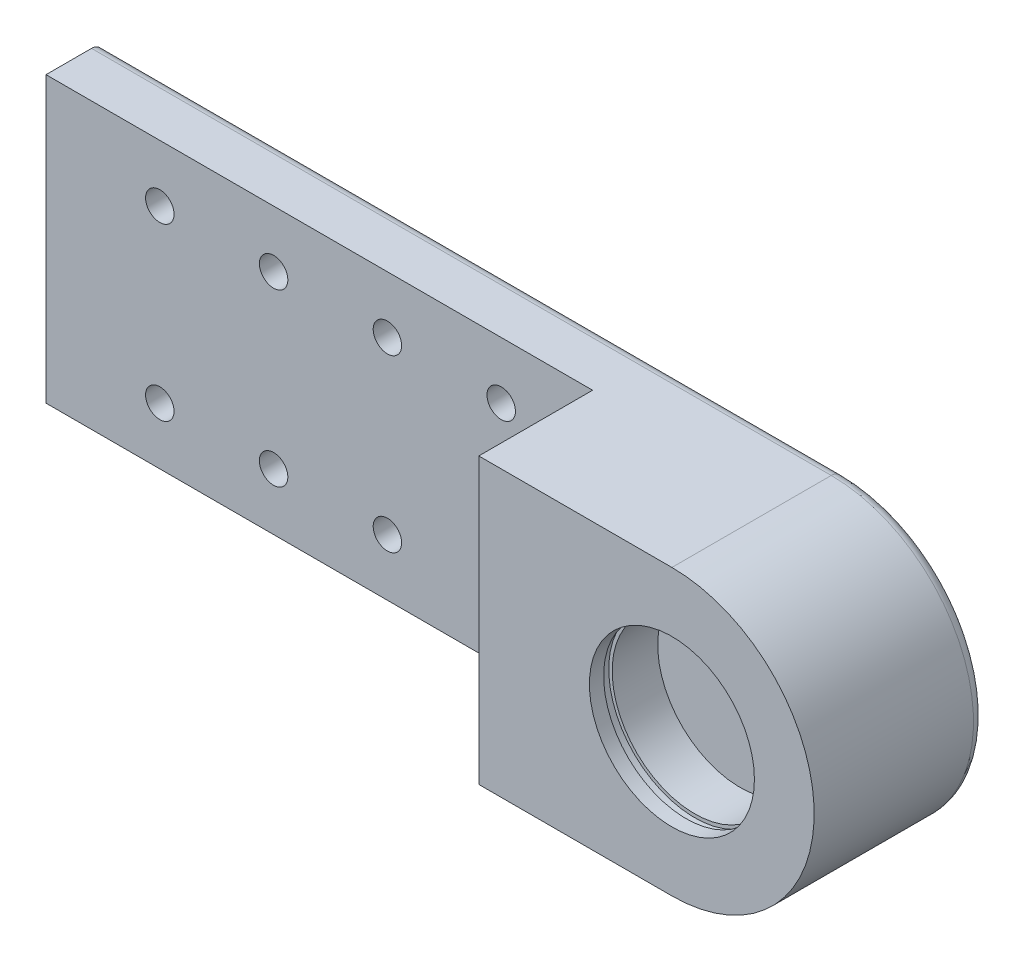
SolidWorks part; units mm, degrees
ref_plane "Front Plane" through (0, 0, 0) normal (0, 0, 1) x (1, 0, 0)
ref_plane "Top Plane" through (0, 0, 0) normal (0, 1, 0) x (1, 0, 0)
ref_plane "Right Plane" through (0, 0, 0) normal (1, 0, 0) x (0, 0, -1)
sketch "Sketch1" plane through (0, 0, 0) normal (0, 0, 1) x (1, 0, 0)
  line L1 (70.1962, 25) -> (-59.8038, 25)
  line L3 (70.1962, -25) -> (-59.8038, -25)
  line L4 (-59.8038, 25) -> (-59.8038, -25)
  circle A2 centre (-39.8038, 15) radius 2.5
  circle A3 centre (-39.8038, -15) radius 2.5
  circle A4 centre (-19.8038, -15) radius 2.5
  circle A5 centre (0.1962, -15) radius 2.5
  circle A6 centre (20.1962, -15) radius 2.5
  circle A7 centre (0.1962, 15) radius 2.5
  circle A8 centre (20.1962, 15) radius 2.5
  circle A9 centre (-19.8038, 15) radius 2.5
  arc A10 (70.1962, -25) -> (70.1962, 25) centre (70.1962, 0) ccw
  point P0 (0, 0)
  point P8 (70.1962, 0)
  point P9 (70.1962, 0)
  point P14 (-59.8038, 0)
  point P26 (-19.8038, 15)
  dimension "D5" = 5
  dimension "D8" = 5
  dimension "D9" = 5
  dimension "D11" = 5
  dimension "D12" = 5
  dimension "D15" = 20
  dimension "D16" = 5
  dimension "D1" = 50
  dimension "D3" = 10
  dimension "D4" = 20
  dimension "D6" = 10
  dimension "D7" = 20
  dimension "D10" = 20
  dimension "D13" = 20
  dimension "D14" = 20
  dimension "D17" = 130
  dimension "D18" = 25
  dimension "D19" = 20
  dimension "D20" = 20
extrude "Boss-Extrude1" add sketch "Sketch1" along normal blind 30
sketch "Sketch4" plane through (0, 0, 0) normal (0, 0, 1) x (1, 0, 0)
  line L0 (36.2567, 25) -> (36.2567, -25)
  line L1 (36.2567, -25) -> (-59.8038, -25)
  line L2 (-59.8038, -25) -> (-59.8038, 25)
  line L3 (-59.8038, 25) -> (36.2567, 25)
extrude "Cut-Extrude3" cut sketch "Sketch4" against normal blind 20 from offset 30
fillet "Fillet1" radius 2 3 edges at (5.1962, -25, 0) (95.1962, 0, 0) (5.1962, 25, 0)
ref_plane "Plane1" through (-59.8038, 0, 0) normal (-1, 0, 0) x (0, 0, 1)
sketch "Sketch5" plane through (-59.8038, 0, 0) normal (-1, 0, 0) x (0, 0, 1)
  circle A0 centre (5, 0) radius 3.175
  dimension "D1" = 6.35
extrude "Cut-Extrude4" cut sketch "Sketch5" against normal blind 10
thread "Thread1" pitch 1.27 method cut profile "Thread Profile1" start angle 0, offset 0, length 10, pitch 1.27, diameter 6.35
ref_plane "Plane2" through (-59.8038, 0, 1.825) normal (0, -1, 0) x (0, 0, -1)
sketch "Thread Profile1" plane through (-59.8038, 0, 1.825) normal (0, -1, 0) x (0, 0, -1)
  line L0 (0, 0) -> (0, 1.27) construction
  line L1 (0, 0) -> (0.6874, 0.3969)
  line L2 (0.6874, 0.3969) -> (0.6874, 0.5556)
  line L3 (0.6874, 0.5556) -> (0, 0.9525)
  line L4 (0.6874, 0.4762) -> (0, 0.4762) construction
  line L11 (0, 0) -> (0, 0.9525)
  point P2 (0, 0)
  dimension "Pitch" = 1.27
  dimension "Profile_Angle" = 60
  dimension "Profile_Land" = 0.1588
  dimension "Profile_Height" = 0.6874
sketch "Sketch6" plane through (0, 0, 0) normal (0, 0, 1) x (1, 0, 0)
  circle A0 centre (70.1962, 0) radius 14.5
  dimension "D1" = 29
extrude "Cut-Extrude5" cut sketch "Sketch6" against normal blind 12 from offset 30
sketch "Sketch7" plane through (0, 0, 0) normal (0, 0, 1) x (1, 0, 0)
  circle A0 centre (70.1962, 0) radius 15.1
  dimension "D1" = 30.2
extrude "Cut-Extrude6" cut sketch "Sketch7" against normal blind 1.5 from offset 27.5
equation "\"1..40mm\"=2"
